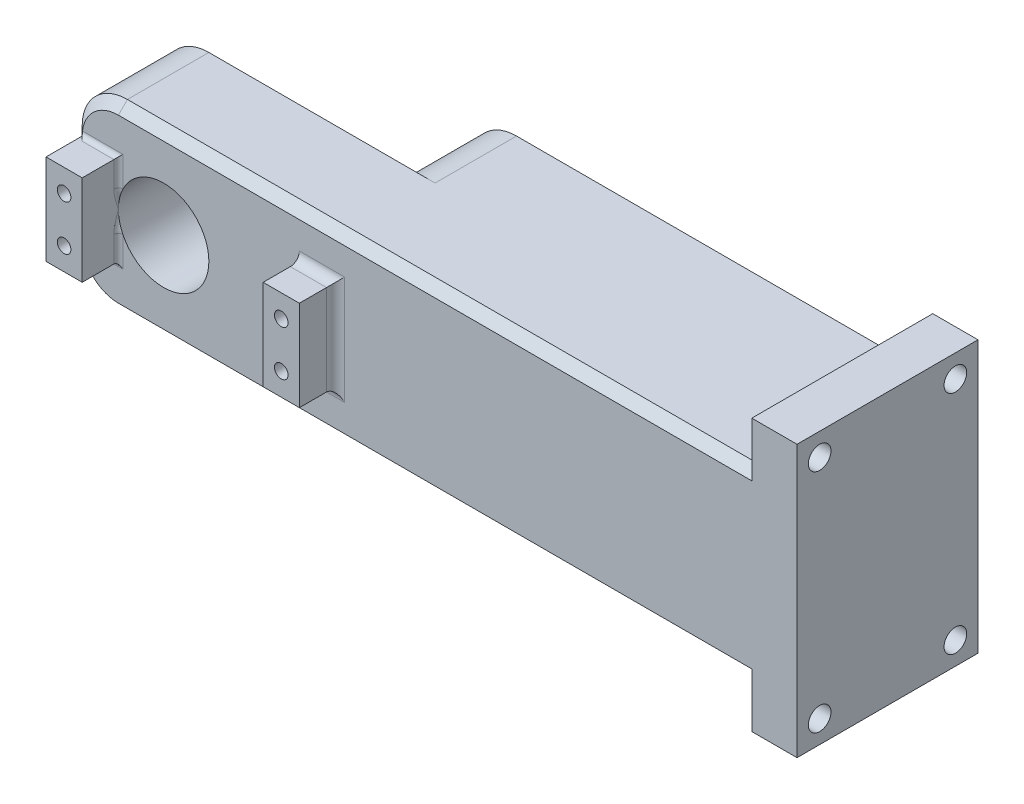
SolidWorks part; units mm, degrees
ref_plane "Front Plane" through (0, 0, 0) normal (0, 0, 1) x (1, 0, 0)
ref_plane "Top Plane" through (0, 0, 0) normal (0, 1, 0) x (1, 0, 0)
ref_plane "Right Plane" through (0, 0, 0) normal (1, 0, 0) x (0, 0, -1)
sketch "Sketch1" plane through (0, 0, 0) normal (0, 0, 1) x (1, 0, 0)
  line L0 (-150, 40) -> (-150, 0)
  line L10 (-150, 0) -> (0, 0)
  line L12 (-150, 40) -> (0, 40)
  line L13 (0, 40) -> (0, 0)
  circle A3 centre (-130, 20) radius 10
  dimension "D3" = 20
  dimension "D12" = 20
  dimension "D14" = 20
  dimension "D2" = 150
  dimension "D6" = 40
extrude "Boss-Extrude1" add sketch "Sketch1" along normal blind 40
ref_plane "Plane1" through (0, 0, 20) normal (0, 0, 1) x (1, 0, 0)
sketch "Sketch3" plane through (0, 0, 0) normal (1, 0, 0) x (0, 0, -1)
  line L0 (-40, 40) -> (0, 40) construction
  line L1 (-40, 50) -> (0, 50)
  line L2 (-40, 50) -> (-40, -10)
  line L3 (-40, -10) -> (0, -10)
  line L4 (0, 50) -> (0, -10)
  line L5 (-40, 0) -> (0, 0) construction
  line L6 (0, 0) -> (0, 40) construction
  circle A0 centre (-5, 45) radius 2.5
  circle A4 centre (-35, 45) radius 2.5
  circle A5 centre (-35, -5) radius 2.5
  circle A6 centre (-5, -5) radius 2.5
  dimension "D3" = 5
  dimension "D4" = 5
  dimension "D5" = 5
  dimension "D7" = 2
  dimension "D8" = 2
  dimension "D1" = 10
  dimension "D2" = 10
  dimension "D6" = 40
extrude "Boss-Extrude2" add sketch "Sketch3" along normal blind 10
sketch "Sketch4" plane through (0, 0, 0) normal (0, -1, 0) x (1, 0, 0)
  line L1 (-150, 0) -> (-100, 0)
  line L2 (-150, 0) -> (-150, 20)
  line L3 (-150, 20) -> (-100, 20)
  line L4 (-100, 0) -> (-100, 20)
  dimension "D1" = 20
  dimension "D2" = 50
extrude "Cut-Extrude1" cut sketch "Sketch4" against normal blind 50
fillet "Fillet1" radius 10 4 edges at (-100, 40, 10) (-100, 0, 10) (-150, 40, 30) (-150, 0, 30)
chamfer "Chamfer1" distance 2 angle 45 10 edges at (-150, 20, 40) (-70, 40, 40) (-70, 0, 40) (-97.0711, 2.9289, 0) (-45, 0, 0) (-45, 40, 0) (-97.0711, 37.0711, 0) (-100, 20, 0) (-147.0711, 37.0711, 40) (-147.0711, 2.9289, 40)
fillet "Fillet2" radius 2 2 edges at (0, 0, 20) (0, 40, 20)
sketch "Sketch5" plane through (0, 0, 40) normal (0, 0, 1) x (1, 0, 0)
  line L1 (-148, 30) -> (-140, 30)
  line L2 (-148, 30) -> (-148, 10)
  line L3 (-148, 10) -> (-140, 10)
  line L4 (-140, 30) -> (-140, 10)
  dimension "D1" = 8
extrude "Boss-Extrude3" add sketch "Sketch5" along normal blind 8
sketch "Sketch6" plane through (0, 0, 48) normal (0, 0, 1) x (1, 0, 0)
  line L0 (-140, 20) -> (-140, 30) construction
  line L1 (-140, 30) -> (-148, 30) construction
  circle A0 centre (-144, 25) radius 1.5
  dimension "D1" = 3
  dimension "D2" = 4
  dimension "D3" = 5
extrude "Cut-Extrude2" cut sketch "Sketch6" against normal blind 5
pattern_linear "LPattern1" count 2 spacing 10 along (0, -1, 0) of "Cut-Extrude2"
pattern_linear "LPattern2" count 2 spacing 48 along (1, 0, 0) of "Boss-Extrude3", "Cut-Extrude2", "LPattern1"
fillet "Fillet3" radius 1 4 edges at (-144, 30, 40) (-140, 25, 40) (-140, 15, 40) (-144, 10, 40)
fillet "Fillet4" radius 2 3 edges at (-96, 30, 40) (-92, 20, 40) (-96, 10, 40)
